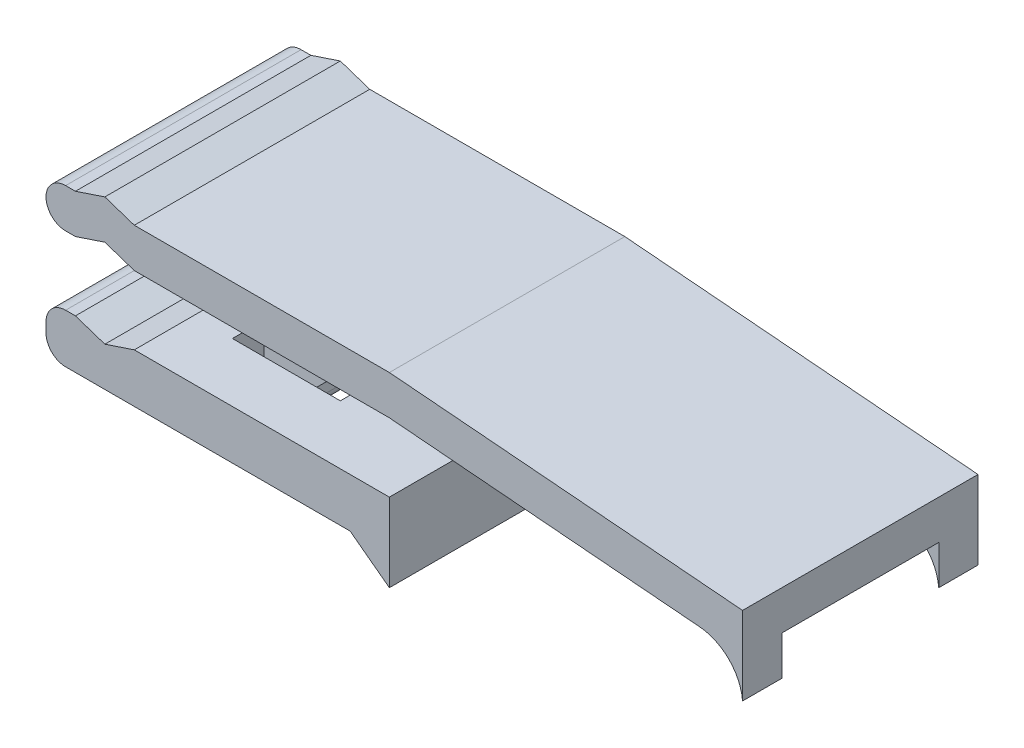
SolidWorks part; units mm, degrees
ref_plane "Front Plane" through (0, 0, 0) normal (0, 0, 1) x (1, 0, 0)
ref_plane "Top Plane" through (0, 0, 0) normal (0, 1, 0) x (1, 0, 0)
ref_plane "Right Plane" through (0, 0, 0) normal (1, 0, 0) x (0, 0, -1)
sketch "Sketch1" plane through (0, 0, 0) normal (0, 0, 1) x (1, 0, 0)
  line L0 (0, 0) -> (0, 4) construction
  line L1 (0, 0) -> (-18, 0) construction
  line L2 (0, 4) -> (-18, 5.5)
  line L3 (-18, 5.5) -> (-31, 5.5)
  line L4 (-31, 5.5) -> (-32.5, 6)
  line L5 (-32.5, 6) -> (-34, 5.5)
  line L6 (-34, 5.5) -> (-35.5, 5.5)
  line L7 (-35.5, 5.5) -> (-35.5, 3.5)
  line L8 (-35.5, -2.5) -> (-20, -2.5)
  line L9 (-20, -2.5) -> (-18, -4)
  line L10 (-35.5, 3.5) -> (-34, 3.5)
  line L11 (-34, 3.5) -> (-32.5, 4)
  line L12 (-18, 0) -> (-18, -4)
  line L13 (-18, 0) -> (-31, 0)
  line L14 (-31, 0) -> (-32.5, -0.5)
  line L15 (-32.5, -0.5) -> (-34, 0)
  line L16 (-34, 0) -> (-35.5, 0)
  line L17 (-35.5, 0) -> (-35.5, -2.5)
  line L18 (-32.5, 4) -> (-31, 3.5)
  line L19 (-31, 3.5) -> (-18, 3.5)
  line L20 (-18, 0) -> (-18, 5.5) construction
  line L21 (-18, 3.5) -> (0, 2)
  line L22 (0, 2) -> (0, 4)
  dimension "D1" = 13
  dimension "D2" = 18
  dimension "D3" = 0.5
  dimension "D4" = 2.5
  dimension "D5" = 1.5
  dimension "D6" = 3.5
  dimension "D7" = 1.5
  dimension "D8" = 2
  dimension "D9" = 0.5
  dimension "D10" = 2
  dimension "D11" = 0.5
  dimension "D12" = 2
  dimension "D13" = 1.5
  dimension "D15" = 3
  dimension "D16" = 1.5
extrude "Boss-Extrude1" add sketch "Sketch1" along normal blind 12
sketch "Sketch2" plane through (0, -2.5, 0) normal (0, -1, 0) x (1, 0, 0)
  line L0 (-20, 12) -> (-20, 0) construction
  line L1 (-29, 9) -> (-23.5, 9)
  line L2 (-29, 9) -> (-29, 3)
  line L3 (-29, 3) -> (-23.5, 3)
  line L4 (-23.5, 9) -> (-23.5, 3)
  line L7 (-20, 6) -> (-35.5, 6) construction
  line L8 (-35.5, 12) -> (-35.5, 0) construction
  point P9 (-23.5, 6)
  dimension "D1" = 3.5
  dimension "D2" = 5.5
  dimension "D3" = 6
extrude "Cut-Extrude1" cut sketch "Sketch2" against normal blind 3
sketch "Sketch3" plane through (0, 0, 3) normal (0, 0, 1) x (1, 0, 0)
  line L0 (-23.5, 0) -> (-25.5, -2)
  line L1 (-25.5, -2) -> (-25.5, -2.5)
  line L2 (-35.5, -2.5) -> (-20, -2.5) construction
  line L3 (-25.5, -2.5) -> (-23.5, -2.5)
  line L4 (-23.5, -2.5) -> (-23.5, 0)
  dimension "D1" = 0.5
  dimension "D2" = 2
extrude "Boss-Extrude2" add sketch "Sketch3" along normal up to surface (6 mm away) up to face at (-26.25, -1.25, 9)
sketch "Sketch4" plane through (0, 0, 12) normal (0, 0, 1) x (1, 0, 0)
  line L0 (-26.7, -2) -> (-24.7, 0)
  line L1 (-18, 0) -> (-31, 0) construction
  line L2 (-24.7, 0) -> (-24.7, 0.5)
  line L3 (-24.7, 0.5) -> (-26.2, 0.5)
  line L4 (-26.2, 0.5) -> (-26.2, 1.2)
  line L5 (-31, 3.5) -> (-18, 3.5) construction
  line L6 (-26.7, -2) -> (-26.7, -3)
  line L7 (-26.7, -3) -> (-27.9, -3)
  line L8 (-27.9, -3) -> (-27.9, 1.2)
  line L10 (-25.5, -2) -> (-25.5, -2.5) construction
  line L11 (-26.2, 1.2) -> (-29.0621, 4.0621) construction
  line L12 (-26.2, 1.2) -> (-23.9, 3.5)
  line L13 (-27.4021, 2.4021) -> (-26.3042, 3.5)
  line L15 (-35.5, -2.5) -> (-20, -2.5) construction
  line L16 (-26.3042, 3.5) -> (-23.9, 3.5)
  arc A0 (-27.4021, 2.4021) -> (-27.9, 1.2) centre (-26.2, 1.2) ccw
  dimension "D1" = 1.5
  dimension "D2" = 1.2
  dimension "D3" = 45
  dimension "D4" = 0.5
  dimension "D5" = 1.2
  dimension "D6" = 1
  dimension "D7" = 2
  dimension "D8" = 0.7
  dimension "D9" = 45
  dimension "D11" = 0.8
  dimension "D13" = 3
  dimension "D14" = 3
extrude "Boss-Extrude3" add sketch "Sketch4" against normal mid plane 5 from offset 6 offset against normal yes
fillet "Fillet7" radius 1 1 edges at (-35.5, 0, 6)
fillet "Fillet8" radius 1 1 edges at (-35.5, 3.5, 6)
fillet "Fillet10" radius 1 1 edges at (-35.5, 5.5, 6)
fillet "Fillet11" radius 1 1 edges at (-35.5, -2.5, 6)
sketch "Sketch5" plane through (0, 0, 12) normal (0, 0, 1) x (1, 0, 0)
  line L0 (0, 2) -> (0, 0)
  line L1 (-18, 3.5) -> (0, 2) construction
  line L2 (-2.1818, 2.1818) -> (0, 2)
  arc A0 (-2.1818, 2.1818) -> (0, 0) centre (-2.3802, -0.1983) cw
extrude "Boss-Extrude4" add sketch "Sketch5" against normal blind 2
extrude "Boss-Extrude5" add sketch "Sketch5<2>" along normal blind 2 from offset 12 offset against normal yes
sketch "Sketch5<2>" plane through (0, 0, 12) normal (0, 0, 1) x (1, 0, 0) same geometry as "Sketch5"
fillet "Fillet12" radius 0.5 2 edges at (-26.7, -3, 6) (-27.9, -3, 6)
fillet "Fillet13" radius 0.5 1 edges at (-26.2, 1.2, 6)
